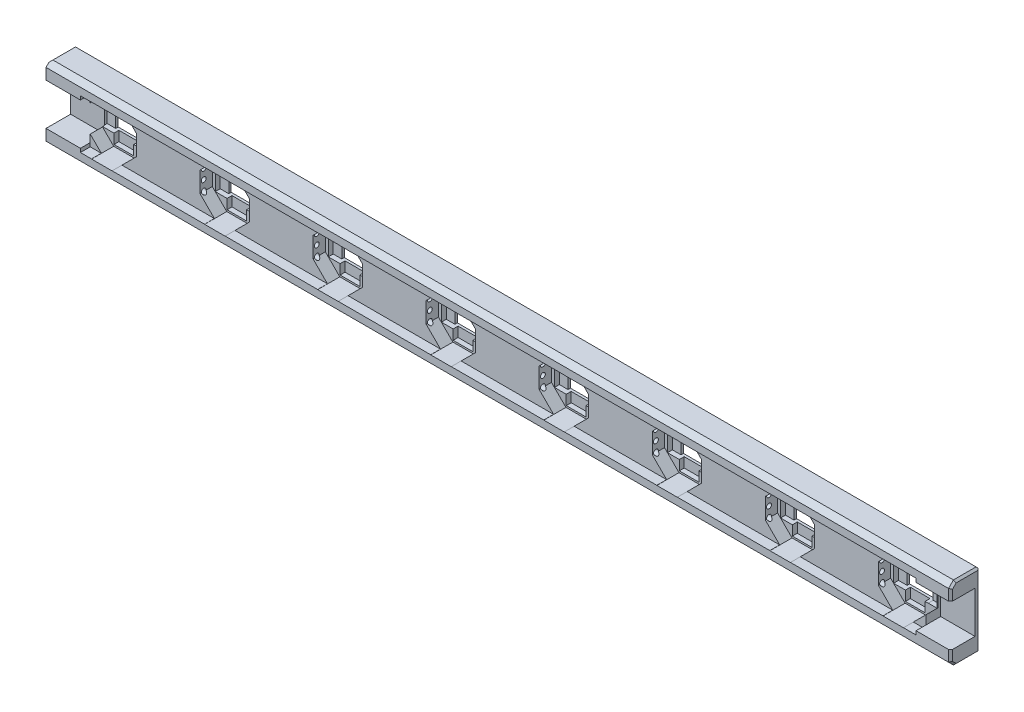
SolidWorks part; units mm, degrees
ref_plane "Front Plane" through (0, 0, 0) normal (0, 0, 1) x (1, 0, 0)
ref_plane "Top Plane" through (0, 0, 0) normal (0, 1, 0) x (1, 0, 0)
ref_plane "Right Plane" through (0, 0, 0) normal (1, 0, 0) x (0, 0, -1)
sketch "Sketch1" plane through (0, 0, 0) normal (0, 0, 1) x (1, 0, 0)
  line L1 (-137.75, 25.6543) -> (46.25, 25.6543)
  line L2 (-137.75, 25.6543) -> (-137.75, 10.6543)
  line L3 (-137.75, 10.6543) -> (46.25, 10.6543)
  line L4 (46.25, 25.6543) -> (46.25, 10.6543)
  dimension "D1" = 184
  dimension "D2" = 15
extrude "Boss-Extrude1" add sketch "Sketch1" along normal blind 6
sketch "Sketch12" plane through (46.25, 0, 0) normal (1, 0, 0) x (0, 0, -1)
  line L0 (-6, 25.6543) -> (-6, 24.6543)
  line L1 (-6, 10.6543) -> (-6, 25.6543) construction
  line L2 (-6, 24.6543) -> (-5, 25.6543)
  line L3 (-6, 25.6543) -> (0, 25.6543) construction
  line L4 (-5, 25.6543) -> (-6, 25.6543)
  line L5 (-6, 10.6543) -> (-5, 10.6543)
  line L6 (-6, 10.6543) -> (0, 10.6543) construction
  line L7 (-5, 10.6543) -> (-6, 11.6543)
  line L8 (-6, 10.6543) -> (-6, 25.6543) construction
  line L9 (-6, 11.6543) -> (-6, 10.6543)
  dimension "D1" = 1
  dimension "D2" = 1
  dimension "D3" = 1
extrude "Cut-Extrude8" cut sketch "Sketch12" against normal up to surface (184 mm away) up to face at (-137.75, 18.1543, 3)
sketch "Sketch13" plane through (0, 0, 0) normal (0, 0, -1) x (-1, 0, 0)
  line L0 (137.75, 25.6543) -> (137.75, 10.6543) construction
  line L1 (135.25, 23.1543) -> (135.75, 23.1543)
  line L2 (135.25, 23.1543) -> (135.25, 13.1543)
  line L3 (135.25, 13.1543) -> (135.75, 13.1543)
  line L4 (135.75, 23.1543) -> (135.75, 13.1543)
  line L5 (-46.25, 25.6543) -> (137.75, 25.6543) construction
  dimension "D1" = 2
  dimension "D2" = 0.5
  dimension "D3" = 10
  dimension "D4" = 2.5
extrude "Cut-Extrude9" cut sketch "Sketch13" against normal blind 0.6
fillet "Fillet1" radius 0.25 1 edges at (-135.75, 18.1543, 0)
fillet "Fillet2" radius 0.25 4 edges at (-135.5, 23.1543, 0.6) (-135.75, 18.1543, 0.6) (-135.5, 13.1543, 0.6) (-135.25, 18.1543, 0.6)
chamfer "Chamfer1" distance 0.4 angle 45 2 edges at (-45.75, 10.6543, 0) (-45.75, 25.6543, 0)
chamfer "Chamfer2" distance 0.4 angle 45 2 edges at (46.25, 18.1543, 0) (-137.75, 18.1543, 0)
chamfer "Chamfer3" distance 0.4 angle 45 2 edges at (-137.75, 10.6543, 2.7) (-137.75, 25.6543, 2.7)
chamfer "Chamfer5" distance 0.4 angle 45 5 edges at (46.25, 25.1543, 5.5) (46.25, 25.6543, 2.7) (46.25, 18.1543, 6) (46.25, 11.1543, 5.5) (46.25, 10.6543, 2.7)
sketch "Sketch15" plane through (0, 0, 6) normal (0, 0, 1) x (1, 0, 0)
  line L0 (-137.75, 24.6543) -> (-137.75, 11.6543) construction
  line L1 (-121.3821, 20.2328) -> (-124.3215, 23.1722)
  line L2 (-124.3215, 23.1722) -> (-128.4785, 23.1722)
  line L3 (-128.4785, 23.1722) -> (-131.4179, 20.2328)
  line L4 (-131.4179, 20.2328) -> (-131.4179, 16.0758)
  line L5 (-131.4179, 16.0758) -> (-128.4785, 13.1364)
  line L6 (-128.4785, 13.1364) -> (-124.3215, 13.1364)
  line L7 (-124.3215, 13.1364) -> (-121.3821, 16.0758)
  line L8 (-121.3821, 16.0758) -> (-121.3821, 20.2328)
  line L9 (-137.35, 25.6543) -> (45.85, 25.6543) construction
  line L10 (-137.75, 11.6543) -> (45.85, 11.6543) construction
  circle A0 centre (-126.4, 18.1543) radius 5.0179 construction
  dimension "D1" = 11.35
  dimension "D2" = 7.5
extrude "Cut-Extrude10" cut sketch "Sketch15" against normal blind 4.5
sketch "Sketch16" plane through (0, 0, 1.5) normal (0, 0, 1) x (1, 0, 0)
  line L1 (-129.0679, 20.7864) -> (-123.7679, 20.7864)
  line L2 (-129.0679, 20.7864) -> (-129.0679, 15.4864)
  line L3 (-129.0679, 15.4864) -> (-123.7679, 15.4864)
  line L4 (-123.7679, 20.7864) -> (-123.7679, 15.4864)
  line L5 (-131.4179, 20.2328) -> (-131.4179, 16.0758) construction
  line L6 (-128.4785, 13.1364) -> (-124.3215, 13.1364) construction
  point P4 (-129.0679, 18.1364)
  point P7 (-131.4179, 18.1543)
  point P10 (-126.4, 13.1364)
  point P11 (-126.4179, 15.4864)
  dimension "D1" = 5.3
  dimension "D2" = 5.3
  dimension "D3" = 2.35
  dimension "D4" = 2.35
extrude "Cut-Extrude11" cut sketch "Sketch16" against normal blind 4.5
sketch "Sketch17" plane through (0, 0, 1.5) normal (0, 0, 1) x (1, 0, 0)
  line L0 (-129.0679, 15.4864) -> (-123.7679, 15.4864) construction
  line L1 (-128.4179, 15.4864) -> (-124.4179, 15.4864)
  line L2 (-128.4179, 15.4864) -> (-128.4179, 13.4864)
  line L3 (-128.4179, 13.4864) -> (-124.4179, 13.4864)
  line L4 (-124.4179, 15.4864) -> (-124.4179, 13.4864)
  line L5 (-123.7679, 20.7864) -> (-129.0679, 20.7864) construction
  line L6 (-128.4179, 20.7864) -> (-124.4179, 20.7864)
  line L7 (-128.4179, 20.7864) -> (-128.4179, 22.7864)
  line L8 (-128.4179, 22.7864) -> (-124.4179, 22.7864)
  line L9 (-124.4179, 20.7864) -> (-124.4179, 22.7864)
  line L10 (-123.7679, 15.4864) -> (-123.7679, 20.7864) construction
  dimension "D1" = 4
  dimension "D2" = 4
  dimension "D3" = 2
  dimension "D4" = 2
  dimension "D5" = 0.65
  dimension "D6" = 0.65
extrude "Cut-Extrude12" cut sketch "Sketch17" against normal blind 1
sketch "Sketch18" plane through (0, 0, 1.5) normal (0, 0, 1) x (1, 0, 0)
  line L1 (-129.0679, 15.4864) -> (-130.8179, 15.4864)
  line L2 (-129.0679, 15.4864) -> (-129.0679, 20.8045)
  line L3 (-129.0679, 20.8045) -> (-130.8179, 20.8045)
  line L4 (-130.8179, 15.4864) -> (-130.8179, 20.8045)
  line L5 (-123.7679, 20.7864) -> (-122.0179, 20.7864)
  line L6 (-123.7679, 20.7864) -> (-123.7679, 15.5045)
  line L7 (-123.7679, 15.5045) -> (-122.0179, 15.5045)
  line L8 (-122.0179, 20.7864) -> (-122.0179, 15.5045)
  dimension "D1" = 1.75
  dimension "D2" = 1.75
extrude "Cut-Extrude13" cut sketch "Sketch18" against normal blind 1
pattern_linear "LPattern1" count 8 spacing 23 along (1, 0, 0) of "Cut-Extrude10", "Cut-Extrude11", "Cut-Extrude12", "Cut-Extrude13"
sketch "Sketch19" plane through (0, 0, 6) normal (0, 0, 1) x (1, 0, 0)
  line L0 (-137.75, 24.6543) -> (-137.75, 11.6543) construction
  line L1 (-137.75, 22.4043) -> (-130.75, 22.4043)
  line L2 (-137.75, 22.4043) -> (-137.75, 13.9043)
  line L3 (-137.75, 13.9043) -> (-130.75, 13.9043)
  line L4 (-130.75, 22.4043) -> (-130.75, 13.9043)
  line L6 (-137.35, 10.6543) -> (45.85, 10.6543) construction
  line L14 (46.25, 24.4886) -> (46.25, 11.82) construction
  line L15 (46.25, 22.4043) -> (39.25, 22.4043)
  line L16 (46.25, 22.4043) -> (46.25, 13.9043)
  line L17 (46.25, 13.9043) -> (39.25, 13.9043)
  line L18 (39.25, 22.4043) -> (39.25, 13.9043)
  dimension "D1" = 8.5
  dimension "D2" = 3.25
  dimension "D3" = 7
  dimension "D4" = 8.5
  dimension "D5" = 7
  dimension "D6" = 3.25
extrude "Cut-Extrude14" cut sketch "Sketch19" against normal blind 5
sketch "Sketch20" plane through (0, 0, 6) normal (0, 0, 1) x (1, 0, 0)
  line L0 (-137.35, 10.6543) -> (45.85, 10.6543) construction
  line L1 (39.25, 13.1543) -> (-130.75, 13.1543)
  line L2 (39.25, 13.1543) -> (39.25, 23.1543)
  line L3 (39.25, 23.1543) -> (-130.75, 23.1543)
  line L4 (-130.75, 13.1543) -> (-130.75, 23.1543)
  line L6 (-130.75, 20.9007) -> (-130.75, 22.4043) construction
  dimension "D1" = 10
  dimension "D2" = 2.5
  dimension "D3" = 0
extrude "Cut-Extrude15" cut sketch "Sketch20" against normal blind 2
sketch "Sketch21" plane through (-62.4179, 0, 0) normal (1, 0, 0) x (0, 0, -1)
  line L1 (-1.5, 20.2328) -> (-4, 20.2328) construction
  line L2 (-4, 16.0758) -> (-4, 20.2328) construction
  circle A0 centre (-3.25, 18.1628) radius 0.5
  circle A1 centre (-3.25, 20.1628) radius 0.5
  circle A2 centre (-3.25, 16.1628) radius 0.5
  dimension "D2" = 1
  dimension "D3" = 1
  dimension "D4" = 1
  dimension "D1" = 2.07
  dimension "D5" = 2
  dimension "D6" = 2
  dimension "D7" = 0.75
extrude "Cut-Extrude16" cut sketch "Sketch21" against normal through all both and the other way through all
